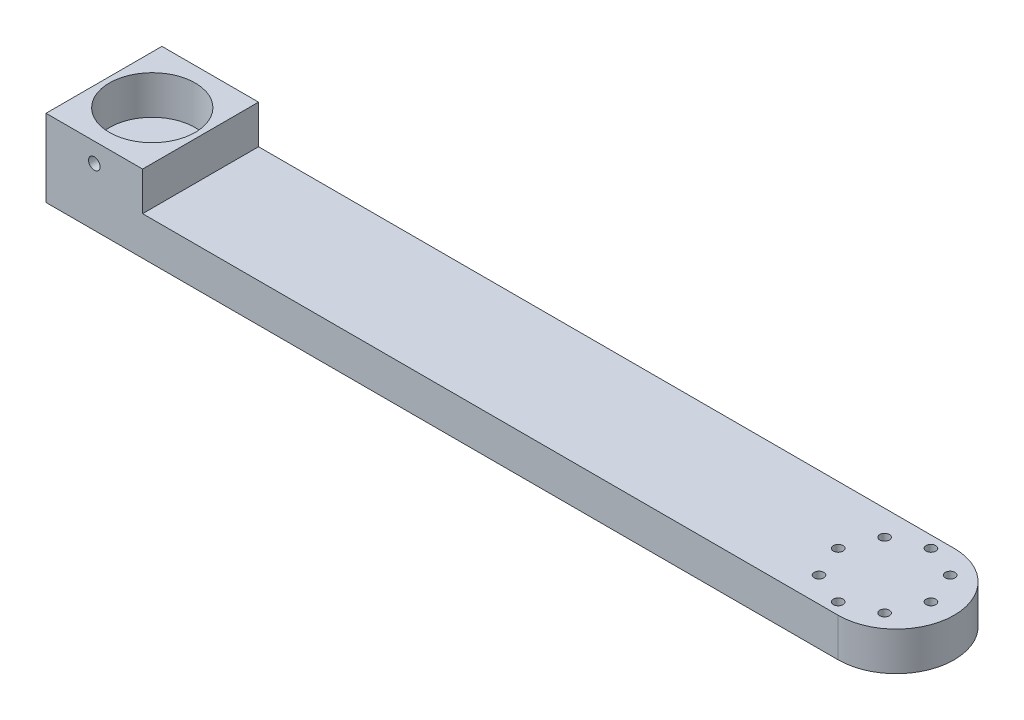
SolidWorks part; units mm, degrees
ref_plane "Front Plane" through (0, 0, 0) normal (0, 0, 1) x (1, 0, 0)
ref_plane "Top Plane" through (0, 0, 0) normal (0, 1, 0) x (1, 0, 0)
ref_plane "Right Plane" through (0, 0, 0) normal (1, 0, 0) x (0, 0, -1)
sketch "Sketch1" plane through (0, 0, 0) normal (0, 1, 0) x (1, 0, 0)
  line L1 (-110, -15) -> (110, -15)
  line L2 (-110, -15) -> (-110, 15)
  line L3 (-110, 15) -> (110, 15)
  line L4 (110, -15) -> (110, 15)
  line L5 (-110, -15) -> (110, 15) construction
  line L6 (-110, 15) -> (110, -15) construction
  circle A0 centre (95, 0) radius 15
  point P0 (0, 0)
  dimension "D3" = 30
  dimension "D1" = 220
  dimension "D2" = 30
extrude "Boss-Extrude1" add sketch "Sketch1" along normal blind 10 contours A0 L3 L2 L1 | A0 region at (-13.3615, 0, 0) region at (95, 0, 0)
sketch "Sketch2" plane through (0, 10, 0) normal (0, 1, 0) x (1, 0, 0)
  line L0 (-5.5, 0) -> (5.5, 0) construction
  line L2 (-85, -15) -> (-110, -15)
  line L3 (-85, -15) -> (-85, 15)
  line L4 (-85, 15) -> (-110, 15)
  line L5 (-110, -15) -> (-110, 15)
  line L6 (-85, -15) -> (-110, 15) construction
  line L7 (-85, 15) -> (-110, -15) construction
  circle A1 centre (-97.5, 0) radius 11.1
  dimension "D1" = 25
  dimension "D2" = 22.2
extrude "Boss-Extrude3" add sketch "Sketch2" along normal blind 10 contours L3 A1 region at (-97.5, 10, 14.6095)
sketch "Sketch4" plane through (0, 10, 0) normal (0, 1, 0) x (1, 0, 0)
  line L1 (-11, 0) -> (11, 0) construction
  line L2 (92, 0) -> (100.4853, 8.4853) construction
  line L3 (100.4853, 8.4853) -> (83.5147, -8.4853) construction
  line L4 (92, 0) -> (100.4853, -8.4853) construction
  line L5 (100.4853, -8.4853) -> (83.5147, 8.4853) construction
  circle A0 centre (92, 12) radius 1.25
  circle A2 centre (92, 0) radius 12 construction
  circle A3 centre (92, -12) radius 1.25
  circle A4 centre (104, 0) radius 1.25
  circle A5 centre (80, 0) radius 1.25
  circle A6 centre (83.5147, 8.4853) radius 1.25
  circle A7 centre (100.4853, 8.4853) radius 1.25
  circle A8 centre (100.4853, -8.4853) radius 1.25
  circle A9 centre (83.5147, -8.4853) radius 1.25
  dimension "D1" = 2.5
  dimension "D3" = 24
sketch "Sketch6" plane through (0, 0, 15) normal (0, 0, 1) x (1, 0, 0)
  line L0 (-85, 10) -> (-110, 10) construction
  line L1 (-110, 20) -> (-110, 0) construction
  line L2 (-97.5, 20) -> (-97.5, 10) construction
  circle A0 centre (-97.5, 15) radius 1.5
  dimension "D1" = 3
extrude "Cut-Extrude2" cut sketch "Sketch6" against normal blind 10
extrude "Cut-Extrude3" cut sketch "Sketch4" along normal blind 16.5 from surface starting at face at (-3.75, 0, 0)
sketch "Sketch8" plane through (0, 10, 0) normal (0, 1, 0) x (1, 0, 0)
  line L0 (100.4853, -8.4853) -> (83.5147, 8.4853) construction
  circle A0 centre (92, 0) radius 6
  dimension "D1" = 12
extrude "Cut-Extrude4" cut sketch "Sketch8" along normal blind 4 from surface starting at face at (92, 0, -10.75)
